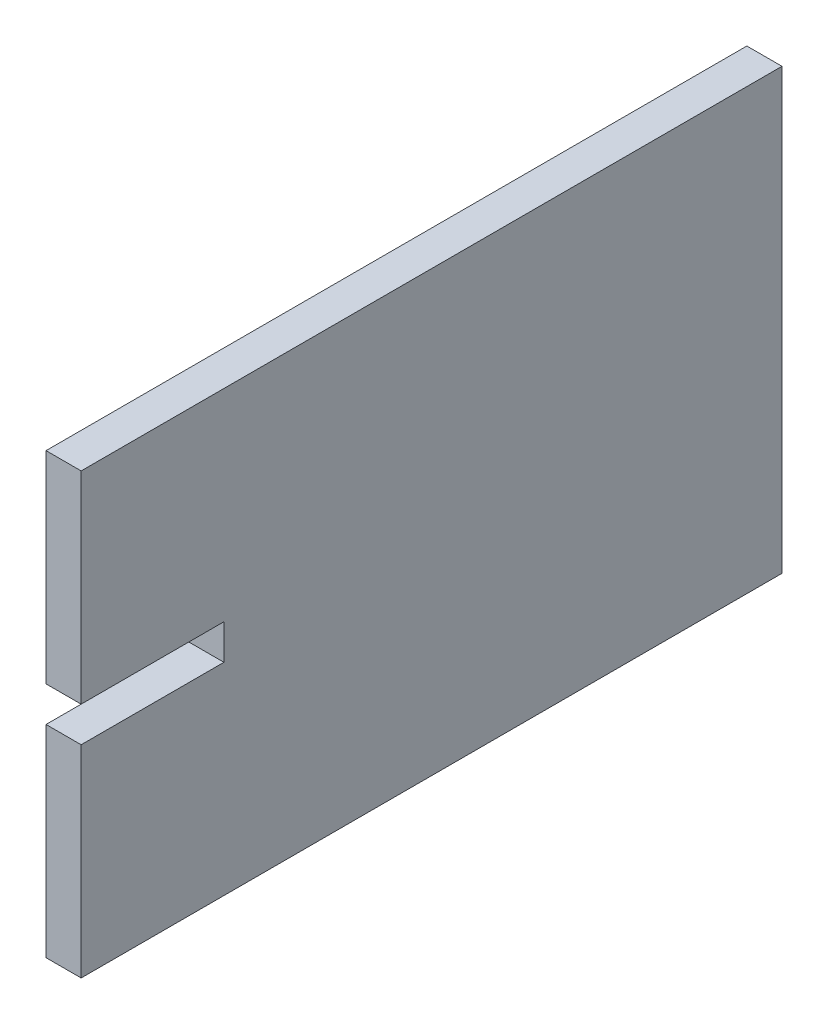
SolidWorks part; units mm, degrees
ref_plane "Front Plane" through (0, 0, 0) normal (0, 0, 1) x (1, 0, 0)
ref_plane "Top Plane" through (0, 0, 0) normal (0, 1, 0) x (1, 0, 0)
ref_plane "Right Plane" through (0, 0, 0) normal (1, 0, 0) x (0, 0, -1)
sketch "Sketch1" plane through (0, 0, 0) normal (1, 0, 0) x (0, 0, -1)
  line L0 (145.7804, 50) -> (145.7804, -50)
  line L1 (145.7804, -50) -> (-13.8065, -50)
  line L2 (-13.8065, -50) -> (-13.8065, -4)
  line L3 (-13.8065, -4) -> (18.7097, -4)
  line L4 (18.7097, -4) -> (18.7097, 4)
  line L5 (18.7097, 4) -> (-13.8065, 4)
  line L6 (-13.8065, 4) -> (-13.8065, 50)
  line L7 (-13.8065, 50) -> (145.7804, 50)
  line L8 (40.1327, 0) -> (-40.1327, 0) construction
  point P2 (145.7804, 0)
  point P9 (13.7097, 0)
  point P10 (145.7804, 50)
  dimension "D1" = 8
  dimension "D2" = 100
  dimension "D3" = 5
extrude "Boss-Extrude1" add sketch "Sketch1" along normal mid plane 8
